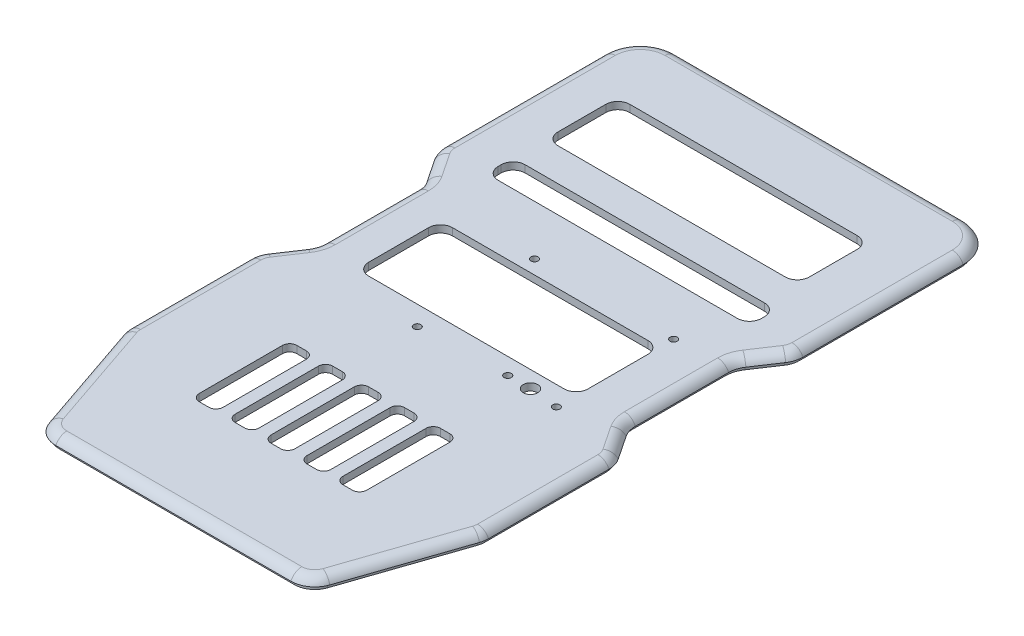
SolidWorks part; units mm, degrees
ref_plane "Front Plane" through (0, 0, 0) normal (0, 0, 1) x (1, 0, 0)
ref_plane "Top Plane" through (0, 0, 0) normal (0, 1, 0) x (1, 0, 0)
ref_plane "Right Plane" through (0, 0, 0) normal (1, 0, 0) x (0, 0, -1)
sketch "Sketch1" plane through (0, 0, 0) normal (0, 1, 0) x (1, 0, 0)
  line L0 (-74.4651, -81.569) -> (-58.5591, -128.2267)
  line L1 (-49.094, -135) -> (49.094, -135)
  line L2 (-73.3205, -22.4808) -> (-66.6795, -12.5192)
  line L3 (-65, -6.9722) -> (-65, 31.9722)
  line L4 (-66.6795, 37.5192) -> (-73.3205, 47.4808)
  line L5 (74.4651, -81.569) -> (58.5591, -128.2267)
  line L6 (73.3205, -22.4808) -> (66.6795, -12.5192)
  line L7 (65, -6.9722) -> (65, 31.9722)
  line L8 (66.6795, 37.5192) -> (73.3205, 47.4808)
  line L9 (75, -28.0278) -> (75, -78.3423)
  line L10 (-75, -28.0278) -> (-75, -78.3423)
  line L11 (75, 53.0278) -> (75, 120)
  line L12 (60, 135) -> (-60, 135)
  line L13 (-75, 120) -> (-75, 53.0278)
  arc A0 (74.4651, -81.569) -> (75, -78.3423) centre (65, -78.3423) ccw
  arc A1 (58.5591, -128.2267) -> (49.094, -135) centre (49.094, -125) cw
  arc A2 (-49.094, -135) -> (-58.5591, -128.2267) centre (-49.094, -125) cw
  arc A3 (-74.4651, -81.569) -> (-75, -78.3423) centre (-65, -78.3423) cw
  arc A4 (-66.6795, -12.5192) -> (-65, -6.9722) centre (-75, -6.9722) ccw
  arc A5 (-65, 31.9722) -> (-66.6795, 37.5192) centre (-75, 31.9722) ccw
  arc A6 (75, -28.0278) -> (73.3205, -22.4808) centre (65, -28.0278) ccw
  arc A7 (66.6795, -12.5192) -> (65, -6.9722) centre (75, -6.9722) cw
  arc A8 (66.6795, 37.5192) -> (65, 31.9722) centre (75, 31.9722) ccw
  arc A9 (75, 53.0278) -> (73.3205, 47.4808) centre (65, 53.0278) cw
  arc A10 (-73.3205, 47.4808) -> (-75, 53.0278) centre (-65, 53.0278) cw
  arc A11 (-75, 120) -> (-60, 135) centre (-60, 120) cw
  arc A12 (75, 120) -> (60, 135) centre (60, 120) ccw
  arc A13 (-75, -28.0278) -> (-73.3205, -22.4808) centre (-65, -28.0278) cw
  dimension "D1" = 65
  dimension "D2" = 135
extrude "Boss-Extrude1" add sketch "Sketch1" along normal blind 3
fillet "Fillet1" radius 5 28 edges at (74.8654, 3, 79.9777) (66.5121, 3, 104.8979) (54.9134, 3, 133.1323) (0, 3, 135) (-54.9134, 3, 133.1323) (-66.5121, 3, 104.8979) (-74.8654, 3, 79.9777) (-75, 3, 53.185) (-74.5709, 3, 25.1299) (-70, 3, 17.5) (-65.4291, 3, 9.8701) (-65, 3, -12.5) (-65.4291, 3, -34.8701) (-70, 3, -42.5) (-74.5709, 3, -50.1299) (-75, 3, -86.5139) (-70.6066, 3, -130.6066) (0, 3, -135) (70.6066, 3, -130.6066) (75, 3, -86.5139) (74.5709, 3, -50.1299) (70, 3, -42.5) (65.4291, 3, -34.8701) (65, 3, -12.5) (65.4291, 3, 9.8701) (70, 3, 17.5) (74.5709, 3, 25.1299) (75, 3, 53.185)
sketch "Sketch2" plane through (0, 0, 0) normal (0, -1, 0) x (1, 0, 0)
  line L14 (-60, -135) -> (60, -135)
  line L15 (75, -120) -> (75, -53.0278)
  line L16 (73.3205, -47.4808) -> (66.6795, -37.5192)
  line L17 (65, -31.9722) -> (65, 6.9722)
  line L18 (66.6795, 12.5192) -> (73.3205, 22.4808)
  line L19 (75, 28.0278) -> (75, 78.3423)
  line L20 (74.4651, 81.569) -> (58.5591, 128.2267)
  line L21 (49.094, 135) -> (-49.094, 135)
  line L22 (-58.5591, 128.2267) -> (-74.4651, 81.569)
  line L23 (-75, 78.3423) -> (-75, 28.0278)
  line L24 (-73.3205, 22.4808) -> (-66.6795, 12.5192)
  line L25 (-65, 6.9722) -> (-65, -31.9722)
  line L26 (-66.6795, -37.5192) -> (-73.3205, -47.4808)
  line L27 (-75, -53.0278) -> (-75, -120)
  line L28 (-60, -135) -> (60, -135)
  line L29 (75, -120) -> (75, -53.0278)
  line L30 (73.3205, -47.4808) -> (66.6795, -37.5192)
  line L31 (65, -31.9722) -> (65, 6.9722)
  line L32 (66.6795, 12.5192) -> (73.3205, 22.4808)
  line L33 (75, 28.0278) -> (75, 78.3423)
  line L34 (74.4651, 81.569) -> (58.5591, 128.2267)
  line L35 (49.094, 135) -> (-49.094, 135)
  line L36 (-58.5591, 128.2267) -> (-74.4651, 81.569)
  line L37 (-75, 78.3423) -> (-75, 28.0278)
  line L38 (-73.3205, 22.4808) -> (-66.6795, 12.5192)
  line L39 (-65, 6.9722) -> (-65, -31.9722)
  line L40 (-66.6795, -37.5192) -> (-73.3205, -47.4808)
  line L41 (-75, -53.0278) -> (-75, -120)
  arc A14 (-75, -120) -> (-60, -135) centre (-60, -120) ccw
  arc A15 (60, -135) -> (75, -120) centre (60, -120) ccw
  arc A16 (75, -53.0278) -> (73.3205, -47.4808) centre (65, -53.0278) ccw
  arc A17 (65, -31.9722) -> (66.6795, -37.5192) centre (75, -31.9722) ccw
  arc A18 (66.6795, 12.5192) -> (65, 6.9722) centre (75, 6.9722) ccw
  arc A19 (73.3205, 22.4808) -> (75, 28.0278) centre (65, 28.0278) ccw
  arc A20 (75, 78.3423) -> (74.4651, 81.569) centre (65, 78.3423) ccw
  arc A21 (58.5591, 128.2267) -> (49.094, 135) centre (49.094, 125) ccw
  arc A22 (-49.094, 135) -> (-58.5591, 128.2267) centre (-49.094, 125) ccw
  arc A23 (-74.4651, 81.569) -> (-75, 78.3423) centre (-65, 78.3423) ccw
  arc A24 (-75, 28.0278) -> (-73.3205, 22.4808) centre (-65, 28.0278) ccw
  arc A25 (-65, 6.9722) -> (-66.6795, 12.5192) centre (-75, 6.9722) ccw
  arc A26 (-66.6795, -37.5192) -> (-65, -31.9722) centre (-75, -31.9722) ccw
  arc A27 (-73.3205, -47.4808) -> (-75, -53.0278) centre (-65, -53.0278) ccw
  arc A28 (-75, -120) -> (-60, -135) centre (-60, -120) ccw
  arc A29 (60, -135) -> (75, -120) centre (60, -120) ccw
  arc A30 (75, -53.0278) -> (73.3205, -47.4808) centre (65, -53.0278) ccw
  arc A31 (65, -31.9722) -> (66.6795, -37.5192) centre (75, -31.9722) ccw
  arc A32 (66.6795, 12.5192) -> (65, 6.9722) centre (75, 6.9722) ccw
  arc A33 (73.3205, 22.4808) -> (75, 28.0278) centre (65, 28.0278) ccw
  arc A34 (75, 78.3423) -> (74.4651, 81.569) centre (65, 78.3423) ccw
  arc A35 (58.5591, 128.2267) -> (49.094, 135) centre (49.094, 125) ccw
  arc A36 (-49.094, 135) -> (-58.5591, 128.2267) centre (-49.094, 125) ccw
  arc A37 (-74.4651, 81.569) -> (-75, 78.3423) centre (-65, 78.3423) ccw
  arc A38 (-75, 28.0278) -> (-73.3205, 22.4808) centre (-65, 28.0278) ccw
  arc A39 (-65, 6.9722) -> (-66.6795, 12.5192) centre (-75, 6.9722) ccw
  arc A40 (-66.6795, -37.5192) -> (-65, -31.9722) centre (-75, -31.9722) ccw
  arc A41 (-73.3205, -47.4808) -> (-75, -53.0278) centre (-65, -53.0278) ccw
  dimension "D1" = 0
sketch "Sketch3" plane through (0, 0, 0) normal (0, -1, 0) x (1, 0, 0)
  line L14 (-60, -135) -> (60, -135)
  line L15 (75, -120) -> (75, -53.0278)
  line L16 (73.3205, -47.4808) -> (66.6795, -37.5192)
  line L17 (65, -31.9722) -> (65, 6.9722)
  line L18 (66.6795, 12.5192) -> (73.3205, 22.4808)
  line L19 (75, 28.0278) -> (75, 78.3423)
  line L20 (74.4651, 81.569) -> (58.5591, 128.2267)
  line L21 (49.094, 135) -> (-49.094, 135)
  line L22 (-58.5591, 128.2267) -> (-74.4651, 81.569)
  line L23 (-75, 78.3423) -> (-75, 28.0278)
  line L24 (-73.3205, 22.4808) -> (-66.6795, 12.5192)
  line L25 (-65, 6.9722) -> (-65, -31.9722)
  line L26 (-66.6795, -37.5192) -> (-73.3205, -47.4808)
  line L27 (-75, -53.0278) -> (-75, -120)
  line L28 (-60, -135) -> (60, -135)
  line L29 (75, -120) -> (75, -53.0278)
  line L30 (73.3205, -47.4808) -> (66.6795, -37.5192)
  line L31 (65, -31.9722) -> (65, 6.9722)
  line L32 (66.6795, 12.5192) -> (73.3205, 22.4808)
  line L33 (75, 28.0278) -> (75, 78.3423)
  line L34 (74.4651, 81.569) -> (58.5591, 128.2267)
  line L35 (49.094, 135) -> (-49.094, 135)
  line L36 (-58.5591, 128.2267) -> (-74.4651, 81.569)
  line L37 (-75, 78.3423) -> (-75, 28.0278)
  line L38 (-73.3205, 22.4808) -> (-66.6795, 12.5192)
  line L39 (-65, 6.9722) -> (-65, -31.9722)
  line L40 (-66.6795, -37.5192) -> (-73.3205, -47.4808)
  line L41 (-75, -53.0278) -> (-75, -120)
  circle A5 centre (54, -129.2797) radius 1.5
  circle A6 centre (-54, -129.2797) radius 1.5
  circle A7 centre (59, -13.2514) radius 1.5
  circle A8 centre (-59, -13.2514) radius 1.5
  circle A9 centre (-0.0469, 129.3714) radius 1.5514
  arc A14 (-75, -120) -> (-60, -135) centre (-60, -120) ccw
  arc A15 (60, -135) -> (75, -120) centre (60, -120) ccw
  arc A16 (75, -53.0278) -> (73.3205, -47.4808) centre (65, -53.0278) ccw
  arc A17 (65, -31.9722) -> (66.6795, -37.5192) centre (75, -31.9722) ccw
  arc A18 (66.6795, 12.5192) -> (65, 6.9722) centre (75, 6.9722) ccw
  arc A19 (73.3205, 22.4808) -> (75, 28.0278) centre (65, 28.0278) ccw
  arc A20 (75, 78.3423) -> (74.4651, 81.569) centre (65, 78.3423) ccw
  arc A21 (58.5591, 128.2267) -> (49.094, 135) centre (49.094, 125) ccw
  arc A22 (-49.094, 135) -> (-58.5591, 128.2267) centre (-49.094, 125) ccw
  arc A23 (-74.4651, 81.569) -> (-75, 78.3423) centre (-65, 78.3423) ccw
  arc A24 (-75, 28.0278) -> (-73.3205, 22.4808) centre (-65, 28.0278) ccw
  arc A25 (-65, 6.9722) -> (-66.6795, 12.5192) centre (-75, 6.9722) ccw
  arc A26 (-66.6795, -37.5192) -> (-65, -31.9722) centre (-75, -31.9722) ccw
  arc A27 (-73.3205, -47.4808) -> (-75, -53.0278) centre (-65, -53.0278) ccw
  arc A28 (-75, -120) -> (-60, -135) centre (-60, -120) ccw
  arc A29 (60, -135) -> (75, -120) centre (60, -120) ccw
  arc A30 (75, -53.0278) -> (73.3205, -47.4808) centre (65, -53.0278) ccw
  arc A31 (65, -31.9722) -> (66.6795, -37.5192) centre (75, -31.9722) ccw
  arc A32 (66.6795, 12.5192) -> (65, 6.9722) centre (75, 6.9722) ccw
  arc A33 (73.3205, 22.4808) -> (75, 28.0278) centre (65, 28.0278) ccw
  arc A34 (75, 78.3423) -> (74.4651, 81.569) centre (65, 78.3423) ccw
  arc A35 (58.5591, 128.2267) -> (49.094, 135) centre (49.094, 125) ccw
  arc A36 (-49.094, 135) -> (-58.5591, 128.2267) centre (-49.094, 125) ccw
  arc A37 (-74.4651, 81.569) -> (-75, 78.3423) centre (-65, 78.3423) ccw
  arc A38 (-75, 28.0278) -> (-73.3205, 22.4808) centre (-65, 28.0278) ccw
  arc A39 (-65, 6.9722) -> (-66.6795, 12.5192) centre (-75, 6.9722) ccw
  arc A40 (-66.6795, -37.5192) -> (-65, -31.9722) centre (-75, -31.9722) ccw
  arc A41 (-73.3205, -47.4808) -> (-75, -53.0278) centre (-65, -53.0278) ccw
  dimension "D1" = 0
sketch "Sketch4" plane through (0, 3, 0) normal (0, 1, 0) x (1, 0, 0)
  line L0 (44.4624, 29.5296) -> (44.4624, -19.4704) construction
  line L1 (44.4624, -19.4704) -> (-13.6276, -19.4704) construction
  line L2 (-13.6276, -19.4704) -> (-13.6276, 29.5296) construction
  line L3 (-13.6276, 29.5296) -> (44.4624, 29.5296) construction
  line L4 (44.4624, 5.0296) -> (-13.6276, 5.0296) construction
  line L5 (15.4174, 29.5296) -> (15.4174, -19.4704) construction
  line L6 (70.4174, 110.0296) -> (-70.4174, 110.0296) construction
  line L19 (-49.094, -130.4174) -> (-1.9055, -130.4174)
  line L20 (1.8117, -130.4174) -> (49.094, -130.4174)
  line L21 (54.2216, -126.7481) -> (70.1276, -80.0904)
  line L22 (70.4174, -78.3423) -> (70.4174, -28.0278)
  line L23 (69.5076, -25.0227) -> (62.8666, -15.0612)
  line L24 (60.4174, -6.9722) -> (60.4174, 11.4401)
  line L25 (60.4174, 15.0628) -> (60.4174, 31.9722)
  line L26 (62.8666, 40.0612) -> (69.5076, 50.0227)
  line L27 (70.4174, 53.0278) -> (70.4174, 120)
  line L28 (60, 130.4174) -> (55.7583, 130.4174)
  line L29 (52.2417, 130.4174) -> (-52.0011, 130.4174)
  line L30 (-55.9989, 130.4174) -> (-60, 130.4174)
  line L31 (-70.4174, 120) -> (-70.4174, 53.0278)
  line L32 (-69.5076, 50.0227) -> (-62.8666, 40.0612)
  line L33 (-60.4174, 31.9722) -> (-60.4174, 15.0628)
  line L34 (-60.4174, 11.4401) -> (-60.4174, -6.9722)
  line L35 (-62.8666, -15.0612) -> (-69.5076, -25.0227)
  line L36 (-70.4174, -28.0278) -> (-70.4174, -78.3423)
  line L37 (-70.1276, -80.0904) -> (-54.2216, -126.7481)
  line L38 (-49.094, -130.4174) -> (-1.9055, -130.4174)
  line L39 (1.8117, -130.4174) -> (49.094, -130.4174)
  line L40 (54.2216, -126.7481) -> (70.1276, -80.0904)
  line L41 (70.4174, -78.3423) -> (70.4174, -28.0278)
  line L42 (69.5076, -25.0227) -> (62.8666, -15.0612)
  line L43 (60.4174, -6.9722) -> (60.4174, 11.4401)
  line L44 (60.4174, 15.0628) -> (60.4174, 31.9722)
  line L45 (62.8666, 40.0612) -> (69.5076, 50.0227)
  line L46 (70.4174, 53.0278) -> (70.4174, 120)
  line L47 (60, 130.4174) -> (55.7583, 130.4174)
  line L48 (52.2417, 130.4174) -> (-52.0011, 130.4174)
  line L49 (-55.9989, 130.4174) -> (-60, 130.4174)
  line L50 (-70.4174, 120) -> (-70.4174, 53.0278)
  line L51 (-69.5076, 50.0227) -> (-62.8666, 40.0612)
  line L52 (-60.4174, 31.9722) -> (-60.4174, 15.0628)
  line L53 (-60.4174, 11.4401) -> (-60.4174, -6.9722)
  line L54 (-62.8666, -15.0612) -> (-69.5076, -25.0227)
  line L55 (-70.4174, -28.0278) -> (-70.4174, -78.3423)
  line L56 (-70.1276, -80.0904) -> (-54.2216, -126.7481)
  circle A4 centre (-13.6276, 29.5296) radius 1.5
  circle A5 centre (-13.6276, -19.4704) radius 1.5
  circle A6 centre (44.4624, -19.4704) radius 1.5
  circle A7 centre (44.4624, 29.5296) radius 1.5
  arc A19 (1.8117, -130.4174) -> (-1.9055, -130.4174) centre (-0.0469, -129.3714) ccw
  arc A20 (49.094, -130.4174) -> (54.2216, -126.7481) centre (49.094, -125) ccw
  arc A21 (70.1276, -80.0904) -> (70.4174, -78.3423) centre (65, -78.3423) ccw
  arc A22 (70.4174, -28.0278) -> (69.5076, -25.0227) centre (65, -28.0278) ccw
  arc A23 (60.4174, -6.9722) -> (62.8666, -15.0612) centre (75, -6.9722) ccw
  arc A24 (60.4174, 15.0628) -> (60.4174, 11.4401) centre (59, 13.2514) ccw
  arc A25 (62.8666, 40.0612) -> (60.4174, 31.9722) centre (75, 31.9722) ccw
  arc A26 (69.5076, 50.0227) -> (70.4174, 53.0278) centre (65, 53.0278) ccw
  arc A27 (70.4174, 120) -> (60, 130.4174) centre (60, 120) ccw
  arc A28 (52.2417, 130.4174) -> (55.7583, 130.4174) centre (54, 129.2797) ccw
  arc A29 (-55.9989, 130.4174) -> (-52.0011, 130.4174) centre (-54, 129.2797) ccw
  arc A30 (-60, 130.4174) -> (-70.4174, 120) centre (-60, 120) ccw
  arc A31 (-70.4174, 53.0278) -> (-69.5076, 50.0227) centre (-65, 53.0278) ccw
  arc A32 (-60.4174, 31.9722) -> (-62.8666, 40.0612) centre (-75, 31.9722) ccw
  arc A33 (-60.4174, 11.4401) -> (-60.4174, 15.0628) centre (-59, 13.2514) ccw
  arc A34 (-62.8666, -15.0612) -> (-60.4174, -6.9722) centre (-75, -6.9722) ccw
  arc A35 (-69.5076, -25.0227) -> (-70.4174, -28.0278) centre (-65, -28.0278) ccw
  arc A36 (-70.4174, -78.3423) -> (-70.1276, -80.0904) centre (-65, -78.3423) ccw
  arc A37 (-54.2216, -126.7481) -> (-49.094, -130.4174) centre (-49.094, -125) ccw
  arc A38 (1.8117, -130.4174) -> (-1.9055, -130.4174) centre (-0.0469, -129.3714) ccw
  arc A39 (49.094, -130.4174) -> (54.2216, -126.7481) centre (49.094, -125) ccw
  arc A40 (70.1276, -80.0904) -> (70.4174, -78.3423) centre (65, -78.3423) ccw
  arc A41 (70.4174, -28.0278) -> (69.5076, -25.0227) centre (65, -28.0278) ccw
  arc A42 (60.4174, -6.9722) -> (62.8666, -15.0612) centre (75, -6.9722) ccw
  arc A43 (60.4174, 15.0628) -> (60.4174, 11.4401) centre (59, 13.2514) ccw
  arc A44 (62.8666, 40.0612) -> (60.4174, 31.9722) centre (75, 31.9722) ccw
  arc A45 (69.5076, 50.0227) -> (70.4174, 53.0278) centre (65, 53.0278) ccw
  arc A46 (70.4174, 120) -> (60, 130.4174) centre (60, 120) ccw
  arc A47 (52.2417, 130.4174) -> (55.7583, 130.4174) centre (54, 129.2797) ccw
  arc A48 (-55.9989, 130.4174) -> (-52.0011, 130.4174) centre (-54, 129.2797) ccw
  arc A49 (-60, 130.4174) -> (-70.4174, 120) centre (-60, 120) ccw
  arc A50 (-70.4174, 53.0278) -> (-69.5076, 50.0227) centre (-65, 53.0278) ccw
  arc A51 (-60.4174, 31.9722) -> (-62.8666, 40.0612) centre (-75, 31.9722) ccw
  arc A52 (-60.4174, 11.4401) -> (-60.4174, 15.0628) centre (-59, 13.2514) ccw
  arc A53 (-62.8666, -15.0612) -> (-60.4174, -6.9722) centre (-75, -6.9722) ccw
  arc A54 (-69.5076, -25.0227) -> (-70.4174, -28.0278) centre (-65, -28.0278) ccw
  arc A55 (-70.4174, -78.3423) -> (-70.1276, -80.0904) centre (-65, -78.3423) ccw
  arc A56 (-54.2216, -126.7481) -> (-49.094, -130.4174) centre (-49.094, -125) ccw
  dimension "D4" = 3
  dimension "D2" = 49
  dimension "D3" = 58.09
  dimension "D5" = 24.5
  dimension "D6" = 55
  dimension "D7" = 140.8348
  dimension "05" = 105
  dimension "D1" = 0
extrude "Cut-Extrude2" cut sketch "Sketch4" against normal blind 4 contours A7 | A4 | A6 | A5 region at (-13.6276, 3, -29.5296) region at (-13.6276, 3, 19.4704) region at (44.4624, 3, 19.4704) region at (44.4624, 3, -29.5296)
sketch "Sketch5" plane through (0, 3, 0) normal (0, 1, 0) x (1, 0, 0)
  circle A2 centre (32.4557, -18.2506) radius 3
  circle A4 centre (22.9305, -18.2506) radius 1.5
  dimension "D1" = 3
extrude "Cut-Extrude3" cut sketch "Sketch5" against normal blind 5
sketch "Sketch7" plane through (0, 3, 0) normal (0, 1, 0) x (1, 0, 0)
  line L19 (-49.094, -130.4174) -> (49.094, -130.4174)
  line L21 (54.2216, -126.7481) -> (70.1276, -80.0904)
  line L22 (70.4174, -78.3423) -> (70.4174, -28.0278)
  line L23 (69.5076, -25.0227) -> (62.8666, -15.0612)
  line L24 (60.4174, -6.9722) -> (60.4174, 31.9722)
  line L26 (62.8666, 40.0612) -> (69.5076, 50.0227)
  line L27 (70.4174, 53.0278) -> (70.4174, 120)
  line L28 (60, 130.4174) -> (-60, 130.4174)
  line L31 (-70.4174, 120) -> (-70.4174, 53.0278)
  line L32 (-69.5076, 50.0227) -> (-62.8666, 40.0612)
  line L33 (-60.4174, 31.9722) -> (-60.4174, -6.9722)
  line L35 (-62.8666, -15.0612) -> (-69.5076, -25.0227)
  line L36 (-70.4174, -28.0278) -> (-70.4174, -78.3423)
  line L37 (-70.1276, -80.0904) -> (-54.2216, -126.7481)
  line L38 (-49.094, -130.4174) -> (49.094, -130.4174)
  line L40 (54.2216, -126.7481) -> (70.1276, -80.0904)
  line L41 (70.4174, -78.3423) -> (70.4174, -28.0278)
  line L42 (69.5076, -25.0227) -> (62.8666, -15.0612)
  line L43 (60.4174, -6.9722) -> (60.4174, 31.9722)
  line L45 (62.8666, 40.0612) -> (69.5076, 50.0227)
  line L46 (70.4174, 53.0278) -> (70.4174, 120)
  line L47 (60, 130.4174) -> (-60, 130.4174)
  line L50 (-70.4174, 120) -> (-70.4174, 53.0278)
  line L51 (-69.5076, 50.0227) -> (-62.8666, 40.0612)
  line L52 (-60.4174, 31.9722) -> (-60.4174, -6.9722)
  line L54 (-62.8666, -15.0612) -> (-69.5076, -25.0227)
  line L55 (-70.4174, -28.0278) -> (-70.4174, -78.3423)
  line L56 (-70.1276, -80.0904) -> (-54.2216, -126.7481)
  arc A20 (49.094, -130.4174) -> (54.2216, -126.7481) centre (49.094, -125) ccw
  arc A21 (70.1276, -80.0904) -> (70.4174, -78.3423) centre (65, -78.3423) ccw
  arc A22 (70.4174, -28.0278) -> (69.5076, -25.0227) centre (65, -28.0278) ccw
  arc A23 (60.4174, -6.9722) -> (62.8666, -15.0612) centre (75, -6.9722) ccw
  arc A25 (62.8666, 40.0612) -> (60.4174, 31.9722) centre (75, 31.9722) ccw
  arc A26 (69.5076, 50.0227) -> (70.4174, 53.0278) centre (65, 53.0278) ccw
  arc A27 (70.4174, 120) -> (60, 130.4174) centre (60, 120) ccw
  arc A30 (-60, 130.4174) -> (-70.4174, 120) centre (-60, 120) ccw
  arc A31 (-70.4174, 53.0278) -> (-69.5076, 50.0227) centre (-65, 53.0278) ccw
  arc A32 (-60.4174, 31.9722) -> (-62.8666, 40.0612) centre (-75, 31.9722) ccw
  arc A34 (-62.8666, -15.0612) -> (-60.4174, -6.9722) centre (-75, -6.9722) ccw
  arc A35 (-69.5076, -25.0227) -> (-70.4174, -28.0278) centre (-65, -28.0278) ccw
  arc A36 (-70.4174, -78.3423) -> (-70.1276, -80.0904) centre (-65, -78.3423) ccw
  arc A37 (-54.2216, -126.7481) -> (-49.094, -130.4174) centre (-49.094, -125) ccw
  arc A39 (49.094, -130.4174) -> (54.2216, -126.7481) centre (49.094, -125) ccw
  arc A40 (70.1276, -80.0904) -> (70.4174, -78.3423) centre (65, -78.3423) ccw
  arc A41 (70.4174, -28.0278) -> (69.5076, -25.0227) centre (65, -28.0278) ccw
  arc A42 (60.4174, -6.9722) -> (62.8666, -15.0612) centre (75, -6.9722) ccw
  arc A44 (62.8666, 40.0612) -> (60.4174, 31.9722) centre (75, 31.9722) ccw
  arc A45 (69.5076, 50.0227) -> (70.4174, 53.0278) centre (65, 53.0278) ccw
  arc A46 (70.4174, 120) -> (60, 130.4174) centre (60, 120) ccw
  arc A49 (-60, 130.4174) -> (-70.4174, 120) centre (-60, 120) ccw
  arc A50 (-70.4174, 53.0278) -> (-69.5076, 50.0227) centre (-65, 53.0278) ccw
  arc A51 (-60.4174, 31.9722) -> (-62.8666, 40.0612) centre (-75, 31.9722) ccw
  arc A53 (-62.8666, -15.0612) -> (-60.4174, -6.9722) centre (-75, -6.9722) ccw
  arc A54 (-69.5076, -25.0227) -> (-70.4174, -28.0278) centre (-65, -28.0278) ccw
  arc A55 (-70.4174, -78.3423) -> (-70.1276, -80.0904) centre (-65, -78.3423) ccw
  arc A56 (-54.2216, -126.7481) -> (-49.094, -130.4174) centre (-49.094, -125) ccw
  dimension "D1" = 0
sketch "Sketch8" plane through (0, 3, 0) normal (0, 1, 0) x (1, 0, 0)
  line L0 (0.2998, -6.0456) -> (0.2998, 64.0598) construction
  line L1 (-49.7002, 61.6544) -> (50.2998, 61.6544)
  line L2 (-54.7002, 56.6544) -> (-54.7002, 55.3789)
  line L3 (-49.7002, 50.3789) -> (50.2998, 50.3789)
  line L4 (55.2998, 56.6544) -> (55.2998, 55.3789)
  line L5 (-20.0126, -54.414) -> (-20.0126, -89.1916)
  line L6 (-49.7002, 105.3816) -> (45.2998, 105.3816)
  line L7 (-54.7002, 100.3816) -> (-54.7002, 80.3816)
  line L8 (-49.7002, 75.3816) -> (45.2998, 75.3816)
  line L9 (50.2998, 100.3816) -> (50.2998, 80.3816)
  line L10 (-32.0126, -51.414) -> (-28.0126, -51.414)
  line L11 (-35.0126, -54.414) -> (-35.0126, -89.1916)
  line L12 (-32.0126, -92.1916) -> (-28.0126, -92.1916)
  line L13 (-25.0126, -54.414) -> (-25.0126, -89.1916)
  line L14 (-17.0126, -51.414) -> (-14.5902, -51.414)
  line L16 (-17.0126, -92.1916) -> (-14.5902, -92.1916)
  line L18 (-42.0926, 23.7086) -> (39.5633, 23.7086)
  line L19 (-47.0926, 18.7086) -> (-47.0926, -6.3185)
  line L20 (-42.0926, -11.3185) -> (39.5633, -11.3185)
  line L21 (44.5633, 18.7086) -> (44.5633, -6.3185)
  line L22 (-17.0126, -51.414) -> (-13.0126, -51.414)
  line L23 (-10.0126, -54.414) -> (-10.0126, -89.1916)
  line L24 (-17.0126, -92.1916) -> (-13.0126, -92.1916)
  line L25 (-5.0126, -54.414) -> (-5.0126, -89.1916)
  line L26 (-2.0126, -51.414) -> (1.9874, -51.414)
  line L27 (4.9874, -54.414) -> (4.9874, -89.1916)
  line L28 (-2.0126, -92.1916) -> (1.9874, -92.1916)
  line L29 (9.9874, -54.414) -> (9.9874, -89.1916)
  line L30 (12.9874, -51.414) -> (16.9874, -51.414)
  line L31 (19.9874, -54.414) -> (19.9874, -89.1916)
  line L32 (12.9874, -92.1916) -> (16.9874, -92.1916)
  line L33 (24.9874, -54.414) -> (24.9874, -89.1916)
  line L34 (27.9874, -51.414) -> (31.9874, -51.414)
  line L35 (34.9874, -54.414) -> (34.9874, -89.1916)
  line L36 (27.9874, -92.1916) -> (31.9874, -92.1916)
  arc A0 (50.2998, 61.6544) -> (55.2998, 56.6544) centre (50.2998, 56.6544) cw
  arc A1 (55.2998, 55.3789) -> (50.2998, 50.3789) centre (50.2998, 55.3789) cw
  arc A2 (-54.7002, 55.3789) -> (-49.7002, 50.3789) centre (-49.7002, 55.3789) ccw
  arc A3 (-54.7002, 56.6544) -> (-49.7002, 61.6544) centre (-49.7002, 56.6544) cw
  circle A4 centre (22.9305, -18.2506) radius 1.5 construction
  circle A5 centre (44.5633, -28.7855) radius 1.5 construction
  circle A6 centre (44.0176, 40.4011) radius 1.5 construction
  circle A7 centre (-42.9797, 39.715) radius 1.5 construction
  circle A8 centre (22.9305, -18.2506) radius 1.5
  circle A9 centre (44.5633, -28.7855) radius 1.5
  circle A10 centre (44.0176, 40.4011) radius 1.5
  circle A11 centre (-42.9797, 39.715) radius 1.5
  arc A12 (45.2998, 105.3816) -> (50.2998, 100.3816) centre (45.2998, 100.3816) cw
  circle A13 centre (-42.434, -29.4716) radius 1.5
  arc A14 (50.2998, 80.3816) -> (45.2998, 75.3816) centre (45.2998, 80.3816) cw
  arc A15 (-49.7002, 75.3816) -> (-54.7002, 80.3816) centre (-49.7002, 80.3816) cw
  arc A16 (-54.7002, 100.3816) -> (-49.7002, 105.3816) centre (-49.7002, 100.3816) cw
  arc A17 (39.5633, 23.7086) -> (44.5633, 18.7086) centre (39.5633, 18.7086) cw
  arc A18 (44.5633, -6.3185) -> (39.5633, -11.3185) centre (39.5633, -6.3185) cw
  arc A19 (-42.0926, -11.3185) -> (-47.0926, -6.3185) centre (-42.0926, -6.3185) cw
  arc A20 (-47.0926, 18.7086) -> (-42.0926, 23.7086) centre (-42.0926, 18.7086) cw
  arc A21 (-25.0126, -89.1916) -> (-28.0126, -92.1916) centre (-28.0126, -89.1916) cw
  arc A22 (-32.0126, -92.1916) -> (-35.0126, -89.1916) centre (-32.0126, -89.1916) cw
  arc A23 (-28.0126, -51.414) -> (-25.0126, -54.414) centre (-28.0126, -54.414) cw
  arc A24 (-35.0126, -54.414) -> (-32.0126, -51.414) centre (-32.0126, -54.414) cw
  arc A25 (-20.0126, -54.414) -> (-17.0126, -51.414) centre (-17.0126, -54.414) cw
  arc A26 (-13.0126, -51.414) -> (-10.0126, -54.414) centre (-13.0126, -54.414) cw
  arc A27 (-10.0126, -89.1916) -> (-13.0126, -92.1916) centre (-13.0126, -89.1916) cw
  arc A28 (-17.0126, -92.1916) -> (-20.0126, -89.1916) centre (-17.0126, -89.1916) cw
  arc A29 (-5.0126, -54.414) -> (-2.0126, -51.414) centre (-2.0126, -54.414) cw
  arc A30 (1.9874, -51.414) -> (4.9874, -54.414) centre (1.9874, -54.414) cw
  arc A31 (4.9874, -89.1916) -> (1.9874, -92.1916) centre (1.9874, -89.1916) cw
  arc A32 (-2.0126, -92.1916) -> (-5.0126, -89.1916) centre (-2.0126, -89.1916) cw
  arc A33 (9.9874, -54.414) -> (12.9874, -51.414) centre (12.9874, -54.414) cw
  arc A34 (16.9874, -51.414) -> (19.9874, -54.414) centre (16.9874, -54.414) cw
  arc A35 (19.9874, -89.1916) -> (16.9874, -92.1916) centre (16.9874, -89.1916) cw
  arc A36 (12.9874, -92.1916) -> (9.9874, -89.1916) centre (12.9874, -89.1916) cw
  arc A37 (24.9874, -54.414) -> (27.9874, -51.414) centre (27.9874, -54.414) cw
  arc A38 (31.9874, -51.414) -> (34.9874, -54.414) centre (31.9874, -54.414) cw
  arc A39 (34.9874, -89.1916) -> (31.9874, -92.1916) centre (31.9874, -89.1916) cw
  arc A40 (27.9874, -92.1916) -> (24.9874, -89.1916) centre (27.9874, -89.1916) cw
  point P50 (-54.7002, 75.3816)
  point P53 (-54.7002, 105.3816)
  dimension "D3" = 5
  dimension "D8" = 5
  dimension "D9" = 5
  dimension "D10" = 3
  dimension "D1" = 55
  dimension "D2" = 55
  dimension "D4" = 55
  dimension "D5" = 50
  dimension "D6" = 30
  dimension "D7" = 81.4272
  dimension "D11" = 10
  dimension "D12" = 5
extrude "Cut-Extrude4" cut sketch "Sketch8" against normal up to next contours A16 L7 A15 L8 A14 L9 A12 L6 | L0 L3 A1 L4 A0 L1 | L3 L0 L1 A3 L2 A2 | A20 L19 A19 L20 A18 L21 A17 L18 | A40 L36 A39 L35 A38 L34 A37 L33 | A36 L32 A35 L31 A34 L30 A33 L29 | A32 L28 A31 L27 A30 L26 A29 L25 | A28 L16 L24 A27 L23 A26 L22 L14 A25 L5 | A24 L11 A22 L12 A21 L13 A23 L10 region at (-26.7357, 3, -56.0167) region at (27.3353, 3, -56.0167) region at (-1.2647, 3, -6.195) region at (-15.0126, 3, 71.8028) region at (-2.2002, 3, -90.3816) region at (-30.0126, 3, 71.8028) region at (-0.0126, 3, 71.8028) region at (14.9874, 3, 71.8028) region at (29.9874, 3, 71.8028)
sketch "Sketch9" plane through (0, 0, 0) normal (0, -1, 0) x (1, 0, 0)
  line L0 (-66.6795, 12.5192) -> (-73.3205, 22.4808) construction
  line L1 (-75, 28.0278) -> (-75, 78.3423) construction
  line L2 (-74.4651, 81.569) -> (-58.5591, 128.2267) construction
  line L3 (-49.094, 135) -> (49.094, 135) construction
  line L4 (-66.6795, 12.5192) -> (-73.3205, 22.4808)
  line L5 (-75, 28.0278) -> (-75, 78.3423)
  line L6 (-74.4651, 81.569) -> (-58.5591, 128.2267)
  line L7 (-49.094, 135) -> (49.094, 135)
  line L8 (58.5591, 128.2267) -> (74.4651, 81.569) construction
  line L9 (75, 78.3423) -> (75, 28.0278) construction
  line L10 (73.3205, 22.4808) -> (66.6795, 12.5192) construction
  line L11 (65, 6.9722) -> (65, -31.9722) construction
  line L12 (66.6795, -37.5192) -> (73.3205, -47.4808) construction
  line L13 (75, -53.0278) -> (75, -120) construction
  line L14 (60, -135) -> (-60, -135) construction
  line L15 (-75, -120) -> (-75, -53.0278) construction
  line L16 (-73.3205, -47.4808) -> (-66.6795, -37.5192) construction
  line L17 (-65, -31.9722) -> (-65, 6.9722) construction
  line L18 (58.5591, 128.2267) -> (74.4651, 81.569)
  line L19 (75, 78.3423) -> (75, 28.0278)
  line L20 (73.3205, 22.4808) -> (66.6795, 12.5192)
  line L21 (65, 6.9722) -> (65, -31.9722)
  line L22 (66.6795, -37.5192) -> (73.3205, -47.4808)
  line L23 (75, -53.0278) -> (75, -120)
  line L24 (60, -135) -> (-60, -135)
  line L25 (-75, -120) -> (-75, -53.0278)
  line L26 (-73.3205, -47.4808) -> (-66.6795, -37.5192)
  line L27 (-65, -31.9722) -> (-65, 6.9722)
  line L28 (-49.094, 133.5) -> (49.094, 133.5)
  line L29 (57.1393, 127.7427) -> (73.0453, 81.085)
  line L30 (73.5, 78.3423) -> (73.5, 28.0278)
  line L31 (72.0724, 23.3128) -> (65.4314, 13.3513)
  line L32 (63.5, 6.9722) -> (63.5, -31.9722)
  line L33 (65.4314, -38.3513) -> (72.0724, -48.3128)
  line L34 (73.5, -53.0278) -> (73.5, -120)
  line L35 (60, -133.5) -> (-60, -133.5)
  line L36 (-73.5, -120) -> (-73.5, -53.0278)
  line L37 (-72.0724, -48.3128) -> (-65.4314, -38.3513)
  line L38 (-63.5, -31.9722) -> (-63.5, 6.9722)
  line L39 (-65.4314, 13.3513) -> (-72.0724, 23.3128)
  line L40 (-73.5, 28.0278) -> (-73.5, 78.3423)
  line L41 (-73.0453, 81.085) -> (-57.1393, 127.7427)
  line L42 (-72, 28.0278) -> (-72, 78.3423)
  line L43 (-71.6256, 80.601) -> (-55.7195, 127.2587)
  line L44 (-49.094, 132) -> (49.094, 132)
  line L45 (55.7195, 127.2587) -> (71.6256, 80.601)
  line L46 (72, 78.3423) -> (72, 28.0278)
  line L47 (70.8244, 24.1449) -> (64.1833, 14.1833)
  line L48 (62, 6.9722) -> (62, -31.9722)
  line L49 (64.1833, -39.1833) -> (70.8244, -49.1449)
  line L50 (72, -53.0278) -> (72, -120)
  line L51 (60, -132) -> (-60, -132)
  line L52 (-72, -120) -> (-72, -53.0278)
  line L53 (-70.8244, -49.1449) -> (-64.1833, -39.1833)
  line L54 (-62, -31.9722) -> (-62, 6.9722)
  line L55 (-64.1833, 14.1833) -> (-70.8244, 24.1449)
  arc A0 (-75, 28.0278) -> (-73.3205, 22.4808) centre (-65, 28.0278) ccw construction
  arc A1 (-74.4651, 81.569) -> (-75, 78.3423) centre (-65, 78.3423) ccw construction
  arc A2 (-49.094, 135) -> (-58.5591, 128.2267) centre (-49.094, 125) ccw construction
  arc A3 (-75, 28.0278) -> (-73.3205, 22.4808) centre (-65, 28.0278) ccw
  arc A4 (-74.4651, 81.569) -> (-75, 78.3423) centre (-65, 78.3423) ccw
  arc A5 (-49.094, 135) -> (-58.5591, 128.2267) centre (-49.094, 125) ccw
  arc A6 (58.5591, 128.2267) -> (49.094, 135) centre (49.094, 125) ccw construction
  arc A7 (75, 78.3423) -> (74.4651, 81.569) centre (65, 78.3423) ccw construction
  arc A8 (73.3205, 22.4808) -> (75, 28.0278) centre (65, 28.0278) ccw construction
  arc A9 (66.6795, 12.5192) -> (65, 6.9722) centre (75, 6.9722) ccw construction
  arc A10 (65, -31.9722) -> (66.6795, -37.5192) centre (75, -31.9722) ccw construction
  arc A11 (75, -53.0278) -> (73.3205, -47.4808) centre (65, -53.0278) ccw construction
  arc A12 (60, -135) -> (75, -120) centre (60, -120) ccw construction
  arc A13 (-75, -120) -> (-60, -135) centre (-60, -120) ccw construction
  arc A14 (-73.3205, -47.4808) -> (-75, -53.0278) centre (-65, -53.0278) ccw construction
  arc A15 (-66.6795, -37.5192) -> (-65, -31.9722) centre (-75, -31.9722) ccw construction
  arc A16 (-65, 6.9722) -> (-66.6795, 12.5192) centre (-75, 6.9722) ccw construction
  arc A17 (58.5591, 128.2267) -> (49.094, 135) centre (49.094, 125) ccw
  arc A18 (75, 78.3423) -> (74.4651, 81.569) centre (65, 78.3423) ccw
  arc A19 (73.3205, 22.4808) -> (75, 28.0278) centre (65, 28.0278) ccw
  arc A20 (66.6795, 12.5192) -> (65, 6.9722) centre (75, 6.9722) ccw
  arc A21 (65, -31.9722) -> (66.6795, -37.5192) centre (75, -31.9722) ccw
  arc A22 (75, -53.0278) -> (73.3205, -47.4808) centre (65, -53.0278) ccw
  arc A23 (60, -135) -> (75, -120) centre (60, -120) ccw
  arc A24 (-75, -120) -> (-60, -135) centre (-60, -120) ccw
  arc A25 (-73.3205, -47.4808) -> (-75, -53.0278) centre (-65, -53.0278) ccw
  arc A26 (-66.6795, -37.5192) -> (-65, -31.9722) centre (-75, -31.9722) ccw
  arc A27 (-65, 6.9722) -> (-66.6795, 12.5192) centre (-75, 6.9722) ccw
  arc A28 (57.1393, 127.7427) -> (49.094, 133.5) centre (49.094, 125) ccw
  arc A29 (73.5, 78.3423) -> (73.0453, 81.085) centre (65, 78.3423) ccw
  arc A30 (72.0724, 23.3128) -> (73.5, 28.0278) centre (65, 28.0278) ccw
  arc A31 (65.4314, 13.3513) -> (63.5, 6.9722) centre (75, 6.9722) ccw
  arc A32 (63.5, -31.9722) -> (65.4314, -38.3513) centre (75, -31.9722) ccw
  arc A33 (73.5, -53.0278) -> (72.0724, -48.3128) centre (65, -53.0278) ccw
  arc A34 (60, -133.5) -> (73.5, -120) centre (60, -120) ccw
  arc A35 (-73.5, -120) -> (-60, -133.5) centre (-60, -120) ccw
  arc A36 (-72.0724, -48.3128) -> (-73.5, -53.0278) centre (-65, -53.0278) ccw
  arc A37 (-65.4314, -38.3513) -> (-63.5, -31.9722) centre (-75, -31.9722) ccw
  arc A38 (-63.5, 6.9722) -> (-65.4314, 13.3513) centre (-75, 6.9722) ccw
  arc A39 (-73.5, 28.0278) -> (-72.0724, 23.3128) centre (-65, 28.0278) ccw
  arc A40 (-73.0453, 81.085) -> (-73.5, 78.3423) centre (-65, 78.3423) ccw
  arc A41 (-49.094, 133.5) -> (-57.1393, 127.7427) centre (-49.094, 125) ccw
  arc A42 (-71.6256, 80.601) -> (-72, 78.3423) centre (-65, 78.3423) ccw
  arc A43 (-49.094, 132) -> (-55.7195, 127.2587) centre (-49.094, 125) ccw
  arc A44 (55.7195, 127.2587) -> (49.094, 132) centre (49.094, 125) ccw
  arc A45 (72, 78.3423) -> (71.6256, 80.601) centre (65, 78.3423) ccw
  arc A46 (70.8244, 24.1449) -> (72, 28.0278) centre (65, 28.0278) ccw
  arc A47 (64.1833, 14.1833) -> (62, 6.9722) centre (75, 6.9722) ccw
  arc A48 (62, -31.9722) -> (64.1833, -39.1833) centre (75, -31.9722) ccw
  arc A49 (72, -53.0278) -> (70.8244, -49.1449) centre (65, -53.0278) ccw
  arc A50 (60, -132) -> (72, -120) centre (60, -120) ccw
  arc A51 (-72, -120) -> (-60, -132) centre (-60, -120) ccw
  arc A52 (-70.8244, -49.1449) -> (-72, -53.0278) centre (-65, -53.0278) ccw
  arc A53 (-64.1833, -39.1833) -> (-62, -31.9722) centre (-75, -31.9722) ccw
  arc A54 (-62, 6.9722) -> (-64.1833, 14.1833) centre (-75, 6.9722) ccw
  arc A55 (-72, 28.0278) -> (-70.8244, 24.1449) centre (-65, 28.0278) ccw
  dimension "D1" = 1.5
  dimension "D2" = 1.5
extrude "Boss-Extrude2" add sketch "Sketch9" along normal blind 2 contours L28 A41 L41 A40 L40 A39 L39 A38 L38 A37 L37 A36 L36 A35 L35 A34 L34 A33 L33 A32 L32 A31 L31 A30 L30 A29 L29 A28 A55 L42 A42 L43 A43 L44 A44 L45 A45 L46 A46 L47 A47 L48 A48 L49 A49 L50 A50 L51 A51 L52 region at (0, 0, 133.1952)
